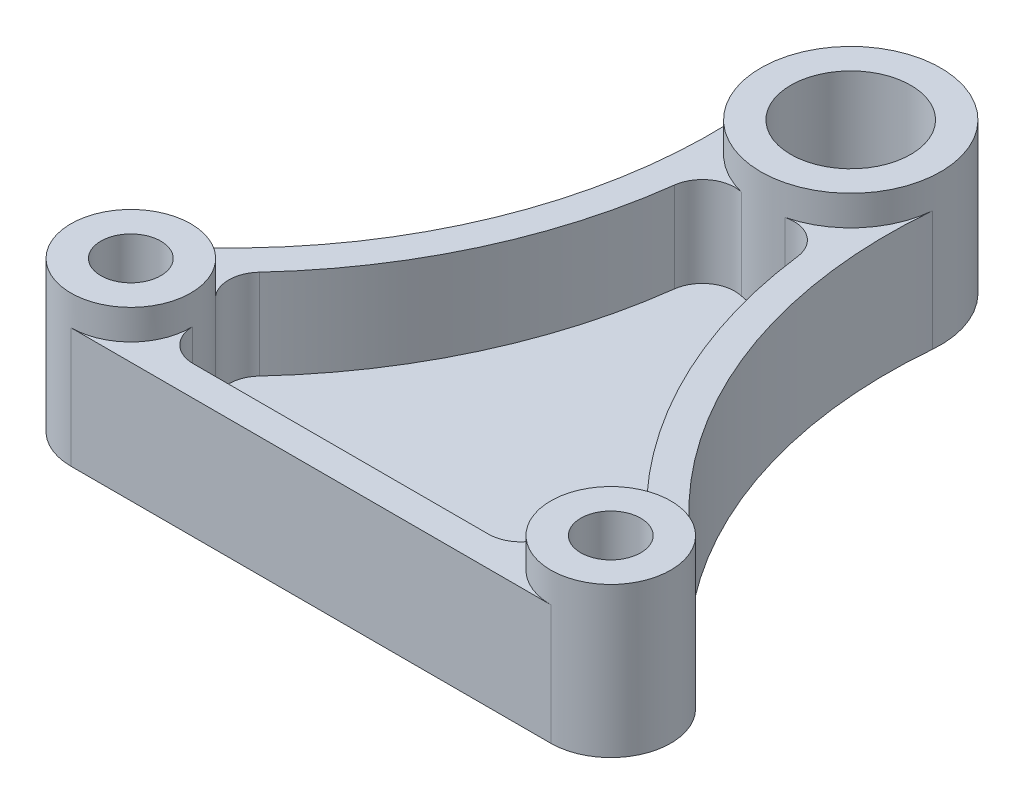
SolidWorks part; units mm, degrees
material "6061-T6 (SS)"
ref_plane "Front Plane" through (0, 0, 0) normal (0, 0, 1) x (1, 0, 0)
ref_plane "Top Plane" through (0, 0, 0) normal (0, 1, 0) x (1, 0, 0)
ref_plane "Right Plane" through (0, 0, 0) normal (1, 0, 0) x (0, 0, -1)
sketch "Outside Cirlces" plane through (0, 0, 0) normal (0, 1, 0) x (1, 0, 0)
  line L0 (0, 0) -> (0, -50.8) construction
  line L1 (0, -50.8) -> (25.4, -50.8) construction
  circle A0 centre (0, 0) radius 9.525
  circle A1 centre (25.4, -50.8) radius 6.35
  circle A2 centre (-25.4, -50.8) radius 6.35
  dimension "D1" = 19.05
  dimension "D2" = 12.7
  dimension "D3" = 50.8
  dimension "D4" = 25.4
sketch "Thru Holes" plane through (0, 0, 0) normal (0, 1, 0) x (1, 0, 0)
  circle A0 centre (0, 0) radius 6.35
  circle A1 centre (25.4, -50.8) radius 3.175
  circle A2 centre (-25.4, -50.8) radius 3.175
  dimension "D1" = 12.7
  dimension "D2" = 6.35
sketch "Profile" plane through (0, 0, 0) normal (0, 1, 0) x (1, 0, 0)
  line L0 (-25.4, -57.15) -> (25.4, -57.15)
  line L2 (0, 0) -> (0, -50.8) construction
  arc A0 (9.4871, -0.8493) -> (29.2539, -45.7532) centre (60.0847, -5.3787) ccw
  circle A1 centre (-25.4, -50.8) radius 6.35
  arc A2 (-29.2539, -45.7532) -> (-25.4, -57.15) centre (-25.4, -50.8) ccw
  circle A3 centre (25.4, -50.8) radius 6.35
  arc A4 (25.4, -57.15) -> (29.2539, -45.7532) centre (25.4, -50.8) ccw
  circle A5 centre (0, 0) radius 9.525
  arc A6 (9.4871, -0.8493) -> (-9.4871, -0.8493) centre (0, 0) ccw
  arc A7 (-9.4871, -0.8493) -> (-29.2539, -45.7532) centre (-60.0847, -5.3787) cw
  dimension "D4" = 50.8
  dimension "D1" = 0
  dimension "D2" = 0
  dimension "D3" = 0
sketch "Sketch1" plane through (0, 0, 0) normal (0, 1, 0) x (1, 0, 0)
  line L1 (-25.4, -57.15) -> (25.4, -57.15)
  line L2 (-25.4, -57.15) -> (25.4, -57.15)
  arc A5 (-29.2539, -45.7532) -> (-25.4, -57.15) centre (-25.4, -50.8) ccw
  arc A6 (25.4, -57.15) -> (29.2539, -45.7532) centre (25.4, -50.8) ccw
  arc A7 (9.4871, -0.8493) -> (29.2539, -45.7532) centre (60.0847, -5.3787) ccw
  arc A8 (9.4871, -0.8493) -> (-9.4871, -0.8493) centre (0, 0) ccw
  arc A9 (-29.2539, -45.7532) -> (-9.4871, -0.8493) centre (-60.0847, -5.3787) ccw
  arc A10 (-29.2539, -45.7532) -> (-25.4, -57.15) centre (-25.4, -50.8) ccw
  arc A11 (25.4, -57.15) -> (29.2539, -45.7532) centre (25.4, -50.8) ccw
  arc A12 (9.4871, -0.8493) -> (29.2539, -45.7532) centre (60.0847, -5.3787) ccw
  arc A13 (9.4871, -0.8493) -> (-9.4871, -0.8493) centre (0, 0) ccw
  arc A14 (-29.2539, -45.7532) -> (-9.4871, -0.8493) centre (-60.0847, -5.3787) ccw
  dimension "D1" = 0
extrude "Boss-Extrude1" add sketch "Sketch1" along normal blind 12.7
extrude "Boss-Extrude2" add sketch "Outside Cirlces" along normal blind 15.875 contours A1 | A2 | A0
sketch "Sketch2" plane through (0, 0, 0) normal (0, 1, 0) x (1, 0, 0)
  circle A0 centre (0, 0) radius 6.35 construction
  circle A1 centre (-25.4, -50.8) radius 3.175 construction
  circle A2 centre (25.4, -50.8) radius 3.175 construction
  circle A3 centre (0, 0) radius 6.35
  circle A4 centre (-25.4, -50.8) radius 3.175
  circle A5 centre (25.4, -50.8) radius 3.175
extrude "Cut-Extrude2" cut sketch "Sketch2" along normal through all
shell "Shell1" thickness 3.175 removed face at (0, 12.7, 35.983)
fillet "Fillet1" radius 3.429 6 edges at (19.9007, 7.9375, 53.975) (-23.2452, 7.9375, 44.8268) (-19.9007, 7.9375, 53.975) (23.2452, 7.9375, 44.8268) (6.1432, 7.9375, 7.2792) (-6.1432, 7.9375, 7.2792)
